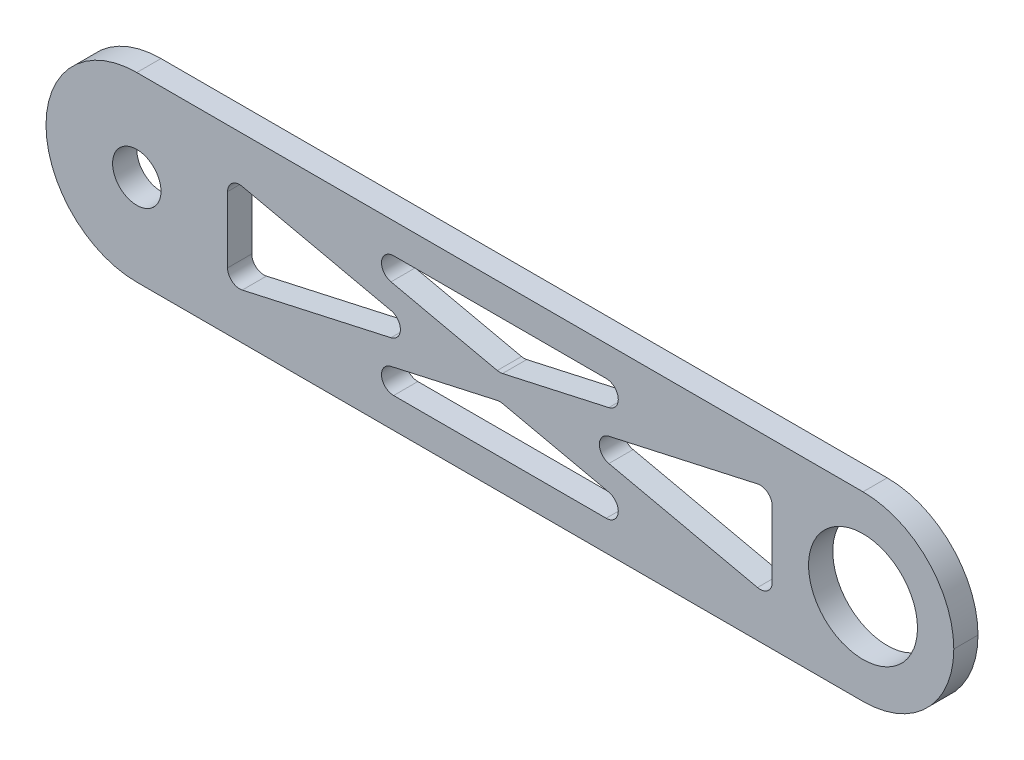
SolidWorks part; units mm, degrees
material "Thornel Mat VMA"
ref_plane "前视基准面" through (0, 0, 0) normal (0, 0, 1) x (1, 0, 0)
ref_plane "上视基准面" through (0, 0, 0) normal (0, 1, 0) x (1, 0, 0)
ref_plane "右视基准面" through (0, 0, 0) normal (1, 0, 0) x (0, 0, -1)
sketch "草图1" plane through (0, 0, 0) normal (0, 0, 1) x (1, 0, 0)
  line L1 (-37.5, -7.5) -> (37.5, -7.5)
  line L2 (-37.5, -7.5) -> (-37.5, 7.5)
  line L3 (-37.5, 7.5) -> (37.5, 7.5)
  line L4 (37.5, -7.5) -> (37.5, 7.5)
  line L5 (-37.5, -7.5) -> (37.5, 7.5) construction
  line L6 (-37.5, 7.5) -> (37.5, -7.5) construction
  point P0 (0, 0)
  dimension "D1" = 75
  dimension "D2" = 15
extrude "凸台-拉伸1" add sketch "草图1" along normal blind 2
fillet "圆角1" radius 7.5 4 edges at (37.5, -7.5, 1) (-37.5, -7.5, 1) (-37.5, 7.5, 1) (37.5, 7.5, 1)
sketch "草图2" plane through (0, 0, 2) normal (0, 0, 1) x (1, 0, 0)
  circle A0 centre (30, 0) radius 4.5
  circle A1 centre (-30, 0) radius 2
  dimension "D1" = 4
  dimension "D2" = 9
  dimension "D3" = 60
extrude "切除-拉伸1" cut sketch "草图2" against normal blind 2
sketch "草图3" plane through (0, 0, 2) normal (0, 0, 1) x (1, 0, 0)
  line L0 (-17.8902, -5) -> (0, -1.0244)
  line L1 (-17.8902, -5) -> (17.8902, -5)
  line L2 (-22.5, -3.9756) -> (-22.5, 3.9756)
  line L3 (-17.8902, 5) -> (17.8902, 5)
  line L4 (22.5, -3.9756) -> (22.5, 3.9756)
  line L5 (-22.5, -5) -> (22.5, 5) construction
  line L6 (-22.5, 5) -> (22.5, -5) construction
  line L7 (-22.5, 3.9756) -> (-4.6098, 0)
  line L8 (-22.5, -3.9756) -> (-4.6098, 0)
  line L9 (-17.8902, 5) -> (0, 1.0244)
  line L10 (4.6098, 0) -> (22.5, 3.9756)
  line L11 (-22.2831, 5.9762) -> (22.7169, -4.0238) construction
  line L12 (-22.7169, -4.0238) -> (22.2831, 5.9762) construction
  line L13 (-22.2831, -5.9762) -> (22.7169, 4.0238) construction
  line L14 (-22.7169, 4.0238) -> (22.2831, -5.9762) construction
  line L15 (4.6098, 0) -> (22.5, -3.9756)
  line L16 (0, 1.0244) -> (17.8902, 5)
  line L17 (0, -1.0244) -> (17.8902, -5)
  point P0 (0, 0)
  dimension "D1" = 45
  dimension "D2" = 10
  dimension "D3" = 1
  dimension "D4" = 1
extrude "切除-拉伸3" cut sketch "草图3" against normal blind 10
fillet "圆角5" radius 1 12 edges at (-17.8902, 5, 1) (17.8902, 5, 1) (0, 1.0244, 1) (-4.6098, 0, 1) (-22.5, -3.9756, 1) (-22.5, 3.9756, 1) (17.8902, -5, 1) (-17.8902, -5, 1) (0, -1.0244, 1) (22.5, 3.9756, 1) (4.6098, 0, 1) (22.5, -3.9756, 1)
